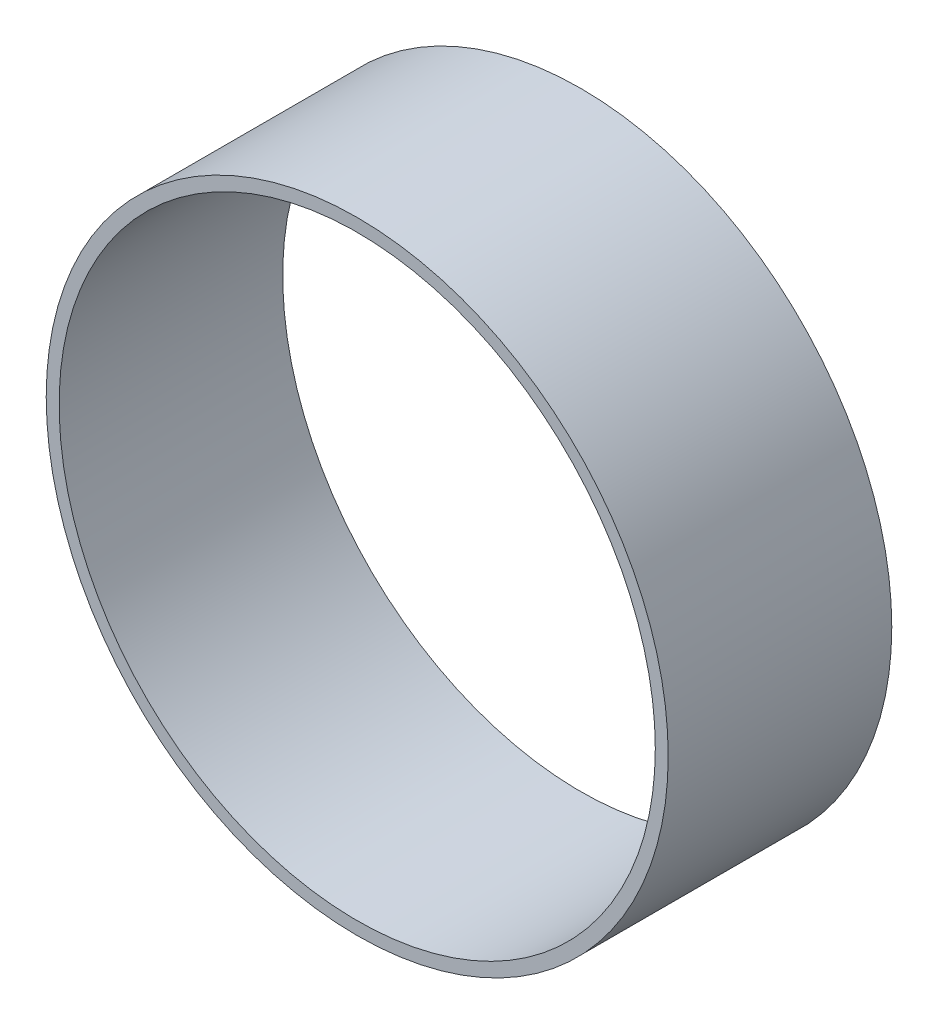
SolidWorks part; units mm, degrees
material "Silicon Dioxide"
ref_plane "Front Plane" through (0, 0, 0) normal (0, 0, 1) x (1, 0, 0)
ref_plane "Top Plane" through (0, 0, 0) normal (0, 1, 0) x (1, 0, 0)
ref_plane "Right Plane" through (0, 0, 0) normal (1, 0, 0) x (0, 0, -1)
sketch "Sketch1" plane through (0, 0, 0) normal (0, 0, 1) x (1, 0, 0)
  circle A0 centre (0, 0) radius 38.1
  circle A1 centre (0, 0) radius 39.75
  dimension "D1" = 76.2
  dimension "D2" = 79.5
extrude "Boss-Extrude1" add sketch "Sketch1" along normal blind 28.575
